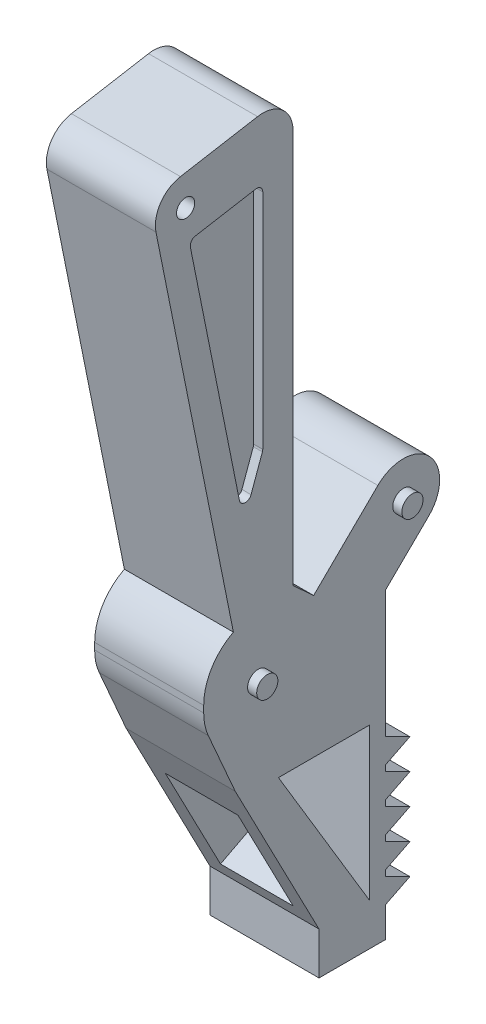
SolidWorks part; units mm, degrees
ref_plane "Front Plane" through (0, 0, 0) normal (0, 0, 1) x (1, 0, 0)
ref_plane "Top Plane" through (0, 0, 0) normal (0, 1, 0) x (1, 0, 0)
ref_plane "Right Plane" through (0, 0, 0) normal (1, 0, 0) x (0, 0, -1)
sketch "Sketch1" plane through (0, 0, 0) normal (1, 0, 0) x (0, 0, -1)
  line L4 (54.1904, 0) -> (40.3929, 68.6268)
  line L5 (40.3929, 68.6268) -> (64.0385, 72.7365)
  line L6 (64.0385, 72.7365) -> (64.0385, 1.7365)
  line L7 (64.0385, 1.7365) -> (54.1904, 0)
  line L8 (54.1904, 0) -> (49.2875, -0.9857)
  line L9 (49.2875, -0.9857) -> (49.2875, -10.9857)
  line L10 (49.2875, -10.9857) -> (54.4904, -22.8992)
  line L11 (54.4904, -22.8992) -> (68.3265, -49.518)
  line L12 (68.3265, -49.518) -> (68.3265, -56.518)
  line L13 (68.3265, -56.518) -> (79.3265, -56.518)
  line L14 (79.3265, -56.518) -> (79.3265, -6.518)
  line L15 (64.0385, 1.7365) -> (67.4364, -1.3807)
  line L17 (79.3265, -6.518) -> (86.4562, 0.4939)
  line L18 (67.4364, -1.3807) -> (78.0418, 9.0496)
  arc A0 (86.4562, 0.4939) -> (78.0418, 9.0496) centre (82.249, 4.7718) ccw
  dimension "D1" = 70
  dimension "D2" = 10
  dimension "D3" = 24
  dimension "D4" = 71
  dimension "D5" = 100
  dimension "D6" = 15
  dimension "D7" = 10
  dimension "D8" = 13
  dimension "D9" = 30
  dimension "D10" = 7
  dimension "D11" = 11
  dimension "D12" = 50
  dimension "D13" = 12
  dimension "D14" = 10
extrude "Boss-Extrude1" add sketch "Sketch1" along normal mid plane 18 contours L7 L6 L5 L4 | L17 A0 L18 L15 L7 L8 L9 L10 L11 L12 L13 L14 region at (0, 40.5668, -55.1908) region at (0, -19.795, -68.9713)
sketch "Sketch3" plane through (9, 0, 0) normal (1, 0, 0) x (0, 0, -1)
  line L0 (76.6265, -49.518) -> (76.6265, -24.518)
  line L1 (76.6265, -24.518) -> (61.6265, -24.518)
  line L2 (61.6265, -24.518) -> (76.6265, -49.518)
  line L3 (79.3265, -56.518) -> (79.3265, -6.518) construction
  line L4 (68.3265, -49.518) -> (76.6265, -49.518) construction
  dimension "D1" = 15
  dimension "D2" = 25
  dimension "D3" = 2.7
extrude "Cut-Extrude1" cut sketch "Sketch3" against normal through all both and the other way through all
sketch "Sketch4" plane through (9, 0, 0) normal (1, 0, 0) x (0, 0, -1)
  line L6 (79.3265, -49.518) -> (83.3265, -49.518)
  line L7 (79.3265, -56.518) -> (79.3265, -6.518) construction
  line L8 (83.3265, -49.518) -> (79.3265, -51.518)
  line L9 (83.3265, -49.518) -> (79.3265, -47.518)
  line M12 (79.3265, -56.518) -> (79.3265, -6.518)
  dimension "D1" = 4
  dimension "D2" = 4
  dimension "D3" = 2
  dimension "D4" = 5
extrude "Boss-Extrude2" add sketch "Sketch4" against normal blind 18 contours L8 L6 M12 | L6 L9 M12 region at (9, -48.8513, -80.6598) region at (9, -50.1847, -80.6598)
pattern_linear "LPattern1" count 5 spacing 5 along (0, 1, 0) of "Boss-Extrude2"
fillet "Fillet1" radius 9 2 edges at (0, -10.9857, -49.2875) (0, -0.9857, -49.2875)
fillet "Fillet2" radius 5 2 edges at (0, 72.7365, -64.0385) (0, 68.6268, -40.3929)
sketch "Sketch5" plane through (9, 0, 0) normal (1, 0, 0) x (0, 0, -1)
  circle A0 centre (46.3067, 64.5796) radius 1.5
  dimension "D1" = 3
extrude "Cut-Extrude2" cut sketch "Sketch5" against normal blind 25
sketch "Sketch8" plane through (0, 17.4279, -33.529) normal (0, -0.4612, 0.8873) x (1, 0, 0)
  line L4 (0, -45.4494) -> (0, -75.4494) construction
  line L5 (9, -45.4494) -> (-9, -45.4494) construction
  line L6 (9, -75.4494) -> (-9, -75.4494) construction
  line L7 (-6, -52.9494) -> (6, -52.9494)
  line L8 (6, -52.9494) -> (6, -72.7069)
  line L9 (6, -72.7069) -> (-6, -72.7069)
  line L10 (-6, -72.7069) -> (-6, -52.9494)
  line L11 (-9, -45.4494) -> (-9, -75.4494) construction
  line L12 (9, -45.4494) -> (9, -75.4494) construction
  point P14 (0, -72.7069)
  dimension "D1" = 7.5
  dimension "D2" = 3
  dimension "D3" = 3
  dimension "D5" = 12
extrude "Cut-Extrude3" cut sketch "Sketch8" against normal up to surface (6.9628 mm away) up to face at (0, -37.018, -69.1265)
sketch "Sketch9" plane through (9, 0, 0) normal (1, 0, 0) x (0, 0, -1)
  circle A0 centre (82.249, 4.7718) radius 1.75
  dimension "D1" = 3.5
extrude "Boss-Extrude3" add sketch "Sketch9" along normal blind 1.5 contours A0
sketch "Sketch10" plane through (9, 0, 0) normal (1, 0, 0) x (0, 0, -1)
  circle A0 centre (58.2875, -9.1062) radius 1.75
  dimension "D1" = 3.5
extrude "Boss-Extrude4" add sketch "Sketch10" along normal blind 1.5
sketch "Sketch11" plane through (9, 0, 0) normal (1, 0, 0) x (0, 0, -1)
  line L0 (45.4505, 69.5058) -> (58.1823, 71.7186) construction
  line L27 (59.0385, 60.5287) -> (59.0385, 23.718)
  line L28 (47.0879, 58.5988) -> (55.1806, 18.3467)
  line L29 (47.8971, 59.7811) -> (57.8672, 61.514)
  line L30 (58.9785, 23.3769) -> (57.101, 18.2027)
  line L31 (54.1904, 0) -> (41.4048, 63.5941) construction
  line L32 (64.0385, 66.7925) -> (64.0385, 1.7365) construction
  arc A0 (55.1806, 18.3467) -> (57.101, 18.2027) centre (56.161, 18.5438) ccw
  arc A1 (59.0385, 23.718) -> (58.9785, 23.3769) centre (58.0385, 23.718) cw
  arc A2 (47.0879, 58.5988) -> (47.8971, 59.7811) centre (48.0683, 58.7959) cw
  arc A3 (57.8672, 61.514) -> (59.0385, 60.5287) centre (58.0385, 60.5287) cw
  point P8 (57.0478, 5.6278)
  dimension "D1" = 1
  dimension "D2" = 1
  dimension "D3" = 5
  dimension "D4" = 4.5871
  dimension "D5" = 10
extrude "Cut-Extrude5" cut sketch "Sketch11" against normal blind 1.5
ref_plane "Plane1" through (0, 0, 0) normal (1, 0, 0) x (0, 0, -1)
mirror "Mirror1" about plane through (0, 0, 0) normal (1, 0, 0) of "Cut-Extrude5"
mirror "Mirror2" about plane through (0, 0, 0) normal (1, 0, 0) of "Boss-Extrude3", "Boss-Extrude4"
